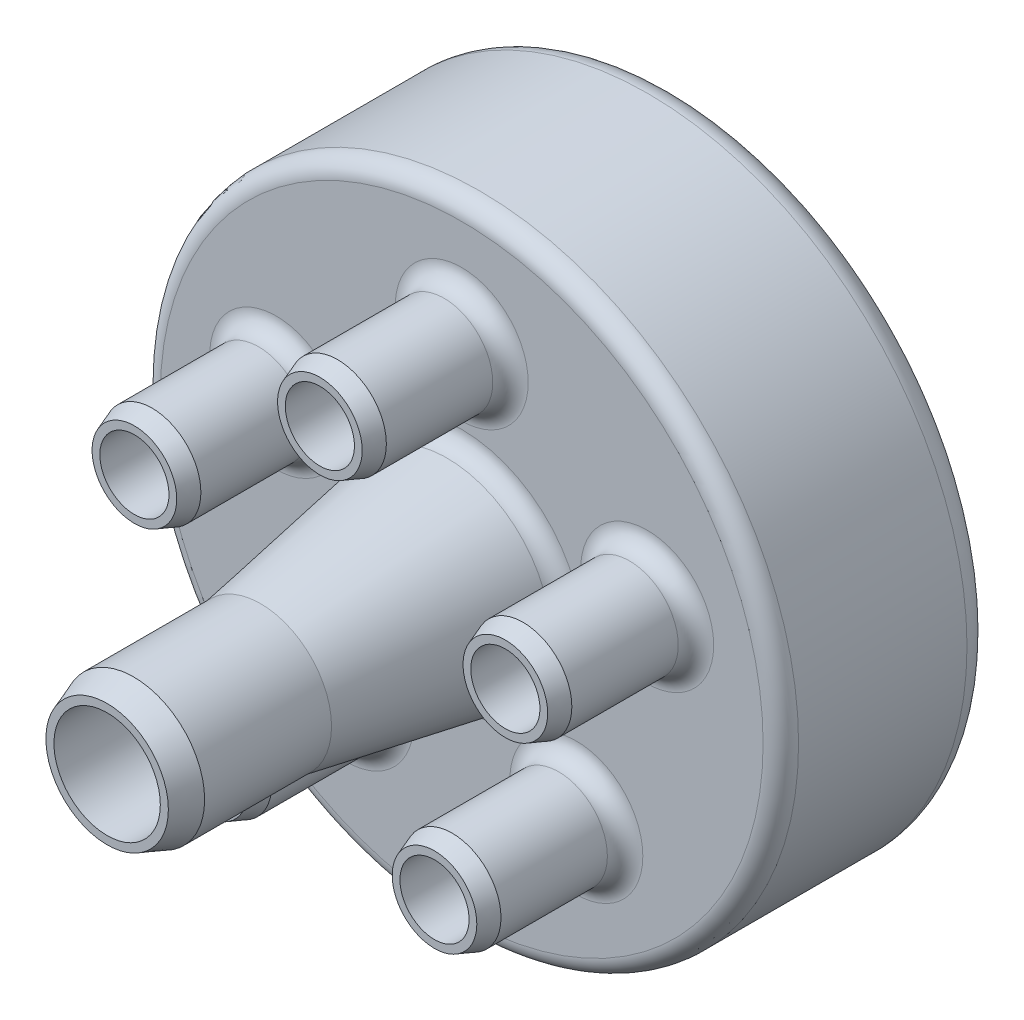
SolidWorks part; units mm, degrees
ref_plane "Front Plane" through (0, 0, 0) normal (0, 0, 1) x (1, 0, 0)
ref_plane "Top Plane" through (0, 0, 0) normal (0, 1, 0) x (1, 0, 0)
ref_plane "Right Plane" through (0, 0, 0) normal (1, 0, 0) x (0, 0, -1)
sketch "Sketch1" plane through (0, 0, 0) normal (0, 0, 1) x (1, 0, 0)
  circle A0 centre (0, 0) radius 18
  circle A1 centre (0, 0) radius 15
  circle A2 centre (0, 0) radius 4
  circle A3 centre (0, 11) radius 2.75
  circle A4 centre (0, 11) radius 1.95
  circle A5 centre (0, 0) radius 3
  dimension "D1" = 30
  dimension "D2" = 8
  dimension "D3" = 5.5
  dimension "D5" = 3
  dimension "D4" = 11
  dimension "D6" = 0.8
  dimension "D7" = 1
extrude "Boss-Extrude1" add sketch "Sketch1" against normal blind 10 contours A0 A1 region at (-17.4909, 0, 0)
extrude "Boss-Extrude2" add sketch "Sketch1<3>" against normal blind 2 contours A4 | A3 A4 | A1 A3 A2 | A2 A5 | A0 A1 region at (-17.4909, 0, 0) region at (-14.5757, 0, 0) region at (-3.8869, 0, 0) region at (-2.6722, 11, 0) region at (0, 11, 0)
sketch "Sketch1<3>" plane through (0, 0, 0) normal (0, 0, 1) x (1, 0, 0) same geometry as "Sketch1"
extrude "Boss-Extrude3" add sketch "Sketch1<4>" along normal blind 8 contours A3 A4 region at (-2.6722, 11, 0)
sketch "Sketch1<4>" plane through (0, 0, 0) normal (0, 0, 1) x (1, 0, 0) same geometry as "Sketch1"
extrude "Boss-Extrude4" add sketch "Sketch1<5>" along normal blind 20 contours A2 A5 region at (-3.8869, 0, 0)
sketch "Sketch1<5>" plane through (0, 0, 0) normal (0, 0, 1) x (1, 0, 0) same geometry as "Sketch1"
sketch "Sketch2" plane through (0, 0, -10) normal (0, 0, -1) x (-1, 0, 0)
  circle A1 centre (0, 0) radius 18
  circle A2 centre (0, 0) radius 18
  dimension "D1" = 0
extrude "Boss-Extrude5" add sketch "Sketch2" along normal blind 2
sketch "Sketch3" plane through (0, 0, 8) normal (0, 0, 1) x (1, 0, 0)
  circle A0 centre (0, 11) radius 1.95 construction
  circle A3 centre (0, 11) radius 1.95
extrude "Cut-Extrude1" cut sketch "Sketch3" against normal up to surface (18 mm away) contours A3 up to face at (15, 0, -10)
fillet "Fillet2" radius 1.5 1 edges at (3, 0, -2)
fillet "Fillet3" radius 1.5 1 edges at (1.95, 11, -2)
pattern_circular "CirPattern2" count 5 over 360 about axis through (0, 0, 20) along (0, 0, -1) of "Fillet3", "Boss-Extrude3", "Cut-Extrude1" reverse direction yes
chamfer "Chamfer1" distance 2 angle 80 1 edges at (4, 0, 0) first distance on face at (11.3114, 0.7838, 0)
fillet "Fillet4" radius 1 7 edges at (18, 0, 0) (2.75, 11, 0) (-9.6118, 6.0146, 0) (-8.6904, -7.2828, 0) (4.2408, -10.5156, 0) (11.3114, 0.7838, 0) (6, 0, 0)
chamfer "Chamfer2" distance 1 angle 20 5 edges at (-9.6118, 6.0146, 8) (-8.6904, -7.2828, 8) (4.2408, -10.5156, 8) (11.3114, 0.7838, 8) (2.75, 11, 8) first distance on face at (-7.7116, 3.3992, 1) first distance on face at (-3.7156, -8.8992, 1) first distance on face at (9.2156, -8.8992, 1) first distance on face at (13.2116, 3.3992, 1) first distance on face at (2.75, 11, 1)
chamfer "Chamfer3" distance 1.5 angle 20 1 edges at (4, 0, 20) first distance on face at (4, 0, 11.3426)
fillet "Fillet5" radius 1.5 1 edges at (-18, 0, -12)
